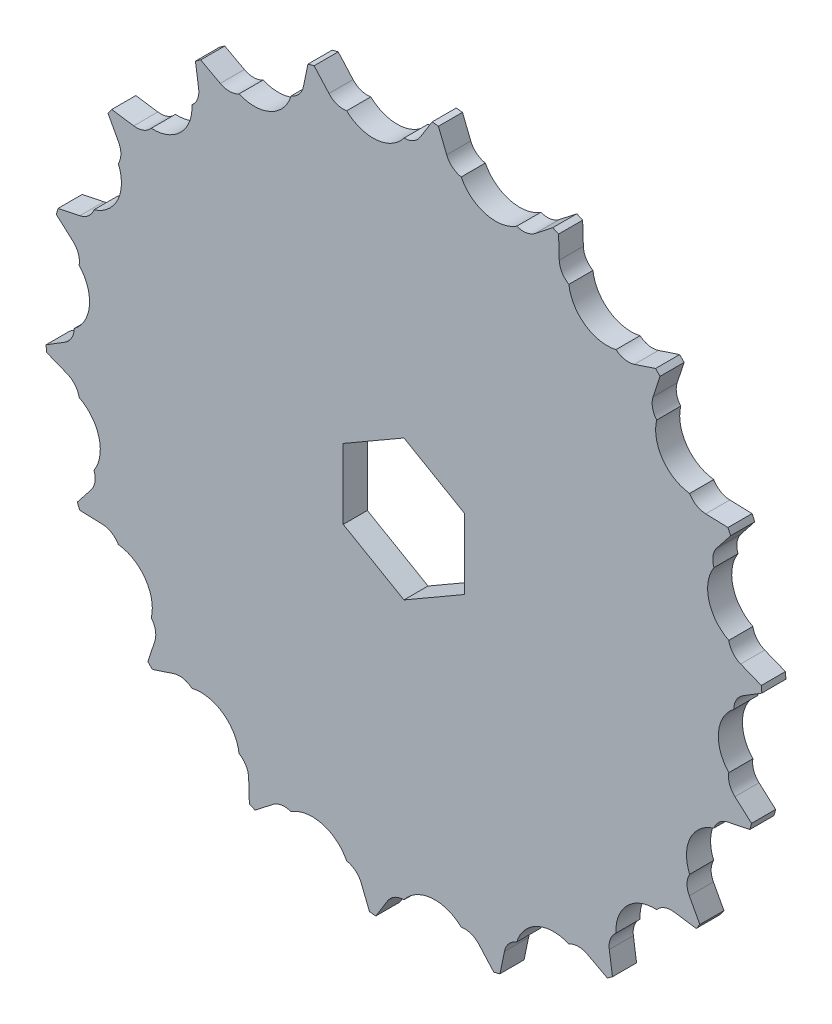
SolidWorks part; units mm, degrees
ref_plane "Front Plane" through (0, 0, 0) normal (0, 0, 1) x (1, 0, 0)
ref_plane "Top Plane" through (0, 0, 0) normal (0, 1, 0) x (1, 0, 0)
ref_plane "Right Plane" through (0, 0, 0) normal (1, 0, 0) x (0, 0, -1)
sketch "Sketch1" plane through (0, 0, 0) normal (0, 0, 1) x (1, 0, 0)
  line L0 (3.4006, 70.3439) -> (6.0855, 74.679)
  line L1 (3.4006, 70.3439) -> (8.8661, 69.8657) construction
  line L2 (6.9749, 74.6012) -> (8.8661, 69.8657)
  line L3 (3.4006, 70.3439) -> (0, 0) construction
  line L4 (0, 0) -> (8.8661, 69.8657) construction
  line L5 (15.5641, 68.6847) -> (18.9609, 72.4877)
  line L6 (19.8233, 72.2567) -> (20.8635, 67.2647)
  line L7 (27.2546, 64.9386) -> (31.2602, 68.094)
  line L8 (32.0693, 67.7166) -> (32.2269, 62.6199)
  line L9 (38.117, 59.2193) -> (42.6097, 61.6312)
  line L10 (43.341, 61.1191) -> (42.6111, 56.0725)
  line L11 (47.8212, 51.7007) -> (52.6645, 53.2958)
  line L12 (53.2958, 52.6645) -> (51.7007, 47.8212)
  line L13 (56.0725, 42.6111) -> (61.1191, 43.341)
  line L14 (61.6312, 42.6097) -> (59.2193, 38.117)
  line L15 (62.6199, 32.2269) -> (67.7166, 32.0693)
  line L16 (68.094, 31.2602) -> (64.9386, 27.2546)
  line L17 (67.2647, 20.8635) -> (72.2567, 19.8233)
  line L18 (72.4877, 18.9609) -> (68.6847, 15.5641)
  line L19 (69.8657, 8.8661) -> (74.6012, 6.9749)
  line L20 (74.679, 6.0855) -> (70.3439, 3.4006)
  line L21 (70.3439, -3.4006) -> (74.679, -6.0855)
  line L22 (74.6012, -6.9749) -> (69.8657, -8.8661)
  line L23 (68.6847, -15.5641) -> (72.4877, -18.9609)
  line L24 (72.2567, -19.8233) -> (67.2647, -20.8635)
  line L25 (64.9386, -27.2546) -> (68.094, -31.2602)
  line L26 (67.7166, -32.0693) -> (62.6199, -32.2269)
  line L27 (59.2193, -38.117) -> (61.6312, -42.6097)
  line L28 (61.1191, -43.341) -> (56.0725, -42.6111)
  line L29 (51.7007, -47.8212) -> (53.2958, -52.6645)
  line L30 (52.6645, -53.2958) -> (47.8212, -51.7007)
  line L31 (42.6111, -56.0725) -> (43.341, -61.1191)
  line L32 (42.6097, -61.6312) -> (38.117, -59.2193)
  line L33 (32.2269, -62.6199) -> (32.0693, -67.7166)
  line L34 (31.2602, -68.094) -> (27.2546, -64.9386)
  line L35 (20.8635, -67.2647) -> (19.8233, -72.2567)
  line L36 (18.9609, -72.4877) -> (15.5641, -68.6847)
  line L37 (8.8661, -69.8657) -> (6.9749, -74.6012)
  line L38 (6.0855, -74.679) -> (3.4006, -70.3439)
  line L39 (-3.4006, -70.3439) -> (-6.0855, -74.679)
  line L40 (-6.9749, -74.6012) -> (-8.8661, -69.8657)
  line L41 (-15.5641, -68.6847) -> (-18.9609, -72.4877)
  line L42 (-19.8233, -72.2567) -> (-20.8635, -67.2647)
  line L43 (-27.2546, -64.9386) -> (-31.2602, -68.094)
  line L44 (-32.0693, -67.7166) -> (-32.2269, -62.6199)
  line L45 (-38.117, -59.2193) -> (-42.6097, -61.6312)
  line L46 (-43.341, -61.1191) -> (-42.6111, -56.0725)
  line L47 (-47.8212, -51.7007) -> (-52.6645, -53.2958)
  line L48 (-53.2958, -52.6645) -> (-51.7007, -47.8212)
  line L49 (-56.0725, -42.6111) -> (-61.1191, -43.341)
  line L50 (-61.6312, -42.6097) -> (-59.2193, -38.117)
  line L51 (-62.6199, -32.2269) -> (-67.7166, -32.0693)
  line L52 (-68.094, -31.2602) -> (-64.9386, -27.2546)
  line L53 (-67.2647, -20.8635) -> (-72.2567, -19.8233)
  line L54 (-72.4877, -18.9609) -> (-68.6847, -15.5641)
  line L55 (-69.8657, -8.8661) -> (-74.6012, -6.9749)
  line L56 (-74.679, -6.0855) -> (-70.3439, -3.4006)
  line L57 (-70.3439, 3.4006) -> (-74.679, 6.0855)
  line L58 (-74.6012, 6.9749) -> (-69.8657, 8.8661)
  line L59 (-68.6847, 15.5641) -> (-72.4877, 18.9609)
  line L60 (-72.2567, 19.8233) -> (-67.2647, 20.8635)
  line L61 (-64.9386, 27.2546) -> (-68.094, 31.2602)
  line L62 (-67.7166, 32.0693) -> (-62.6199, 32.2269)
  line L63 (-59.2193, 38.117) -> (-61.6312, 42.6097)
  line L64 (-61.1191, 43.341) -> (-56.0725, 42.6111)
  line L65 (-51.7007, 47.8212) -> (-53.2958, 52.6645)
  line L66 (-52.6645, 53.2958) -> (-47.8212, 51.7007)
  line L67 (-42.6111, 56.0725) -> (-43.341, 61.1191)
  line L68 (-42.6097, 61.6312) -> (-38.117, 59.2193)
  line L69 (-32.2269, 62.6199) -> (-32.0693, 67.7166)
  line L70 (-31.2602, 68.094) -> (-27.2546, 64.9386)
  line L71 (-20.8635, 67.2647) -> (-19.8233, 72.2567)
  line L72 (-18.9609, 72.4877) -> (-15.5641, 68.6847)
  line L73 (-8.8661, 69.8657) -> (-6.9749, 74.6012)
  line L74 (-6.0855, 74.679) -> (-3.4006, 70.3439)
  line L83 (0, 72.45) -> (0, 0) construction
  line L84 (0, 0) -> (6.5105, 74.4157) construction
  circle A0 centre (0, 0) radius 72.45 construction
  arc A1 (-3.9985, 72.3396) -> (3.4006, 70.3439) centre (0, 72.45) ccw
  arc A2 (4.6139, 72.3029) -> (8.0115, 72.0057) centre (0, 0) cw
  arc A3 (6.0855, 74.679) -> (6.9749, 74.6012) centre (6.5105, 74.4157) cw
  arc A4 (8.6239, 71.9349) -> (15.5641, 68.6847) centre (12.5808, 71.3493) ccw
  arc A5 (18.9609, 72.4877) -> (19.8233, 72.2567) centre (19.3338, 72.1547) cw
  arc A6 (20.9843, 69.3445) -> (27.2546, 64.9386) centre (24.7794, 68.0807) ccw
  arc A7 (31.2602, 68.094) -> (32.0693, 67.7166) centre (31.5696, 67.7012) cw
  arc A8 (32.707, 64.6472) -> (38.117, 59.2193) centre (36.225, 62.7435) ccw
  arc A9 (42.6097, 61.6312) -> (43.341, 61.1191) centre (42.8462, 61.1907) cw
  arc A10 (43.436, 57.9855) -> (47.8212, 51.7007) centre (46.57, 55.4999) ccw
  arc A11 (52.6645, 53.2958) -> (53.2958, 52.6645) centre (52.8209, 52.8209) cw
  arc A12 (52.8452, 49.562) -> (56.0725, 42.6111) centre (55.4999, 46.57) ccw
  arc A13 (61.1191, 43.341) -> (61.6312, 42.6097) centre (61.1907, 42.8462) cw
  arc A14 (60.6487, 39.6326) -> (62.6199, 32.2269) centre (62.7435, 36.225) ccw
  arc A15 (67.7166, 32.0693) -> (68.094, 31.2602) centre (67.7012, 31.5696) cw
  arc A16 (66.6094, 28.4989) -> (67.2647, 20.8635) centre (68.0807, 24.7794) ccw
  arc A17 (72.2567, 19.8233) -> (72.4877, 18.9609) centre (72.1547, 19.3338) cw
  arc A18 (70.5463, 16.4994) -> (69.8657, 8.8661) centre (71.3493, 12.5808) ccw
  arc A19 (74.6012, 6.9749) -> (74.679, 6.0855) centre (74.4157, 6.5105) cw
  arc A20 (72.3396, 3.9985) -> (70.3439, -3.4006) centre (72.45, 0) ccw
  arc A21 (74.679, -6.0855) -> (74.6012, -6.9749) centre (74.4157, -6.5105) cw
  arc A22 (71.9349, -8.6239) -> (68.6847, -15.5641) centre (71.3493, -12.5808) ccw
  arc A23 (72.4877, -18.9609) -> (72.2567, -19.8233) centre (72.1547, -19.3338) cw
  arc A24 (69.3445, -20.9843) -> (64.9386, -27.2546) centre (68.0807, -24.7794) ccw
  arc A25 (68.094, -31.2602) -> (67.7166, -32.0693) centre (67.7012, -31.5696) cw
  arc A26 (64.6472, -32.707) -> (59.2193, -38.117) centre (62.7435, -36.225) ccw
  arc A27 (61.6312, -42.6097) -> (61.1191, -43.341) centre (61.1907, -42.8462) cw
  arc A28 (57.9855, -43.436) -> (51.7007, -47.8212) centre (55.4999, -46.57) ccw
  arc A29 (53.2958, -52.6645) -> (52.6645, -53.2958) centre (52.8209, -52.8209) cw
  arc A30 (49.562, -52.8452) -> (42.6111, -56.0725) centre (46.57, -55.4999) ccw
  arc A31 (43.341, -61.1191) -> (42.6097, -61.6312) centre (42.8462, -61.1907) cw
  arc A32 (39.6326, -60.6487) -> (32.2269, -62.6199) centre (36.225, -62.7435) ccw
  arc A33 (32.0693, -67.7166) -> (31.2602, -68.094) centre (31.5696, -67.7012) cw
  arc A34 (28.4989, -66.6094) -> (20.8635, -67.2647) centre (24.7794, -68.0807) ccw
  arc A35 (19.8233, -72.2567) -> (18.9609, -72.4877) centre (19.3338, -72.1547) cw
  arc A36 (16.4994, -70.5463) -> (8.8661, -69.8657) centre (12.5808, -71.3493) ccw
  arc A37 (6.9749, -74.6012) -> (6.0855, -74.679) centre (6.5105, -74.4157) cw
  arc A38 (3.9985, -72.3396) -> (-3.4006, -70.3439) centre (0, -72.45) ccw
  arc A39 (-6.0855, -74.679) -> (-6.9749, -74.6012) centre (-6.5105, -74.4157) cw
  arc A40 (-8.6239, -71.9349) -> (-15.5641, -68.6847) centre (-12.5808, -71.3493) ccw
  arc A41 (-18.9609, -72.4877) -> (-19.8233, -72.2567) centre (-19.3338, -72.1547) cw
  arc A42 (-20.9843, -69.3445) -> (-27.2546, -64.9386) centre (-24.7794, -68.0807) ccw
  arc A43 (-31.2602, -68.094) -> (-32.0693, -67.7166) centre (-31.5696, -67.7012) cw
  arc A44 (-32.707, -64.6472) -> (-38.117, -59.2193) centre (-36.225, -62.7435) ccw
  arc A45 (-42.6097, -61.6312) -> (-43.341, -61.1191) centre (-42.8462, -61.1907) cw
  arc A46 (-43.436, -57.9855) -> (-47.8212, -51.7007) centre (-46.57, -55.4999) ccw
  arc A47 (-52.6645, -53.2958) -> (-53.2958, -52.6645) centre (-52.8209, -52.8209) cw
  arc A48 (-52.8452, -49.562) -> (-56.0725, -42.6111) centre (-55.4999, -46.57) ccw
  arc A49 (-61.1191, -43.341) -> (-61.6312, -42.6097) centre (-61.1907, -42.8462) cw
  arc A50 (-60.6487, -39.6326) -> (-62.6199, -32.2269) centre (-62.7435, -36.225) ccw
  arc A51 (-67.7166, -32.0693) -> (-68.094, -31.2602) centre (-67.7012, -31.5696) cw
  arc A52 (-66.6094, -28.4989) -> (-67.2647, -20.8635) centre (-68.0807, -24.7794) ccw
  arc A53 (-72.2567, -19.8233) -> (-72.4877, -18.9609) centre (-72.1547, -19.3338) cw
  arc A54 (-70.5463, -16.4994) -> (-69.8657, -8.8661) centre (-71.3493, -12.5808) ccw
  arc A55 (-74.6012, -6.9749) -> (-74.679, -6.0855) centre (-74.4157, -6.5105) cw
  arc A56 (-72.3396, -3.9985) -> (-70.3439, 3.4006) centre (-72.45, 0) ccw
  arc A57 (-74.679, 6.0855) -> (-74.6012, 6.9749) centre (-74.4157, 6.5105) cw
  arc A58 (-71.9349, 8.6239) -> (-68.6847, 15.5641) centre (-71.3493, 12.5808) ccw
  arc A59 (-72.4877, 18.9609) -> (-72.2567, 19.8233) centre (-72.1547, 19.3338) cw
  arc A60 (-69.3445, 20.9843) -> (-64.9386, 27.2546) centre (-68.0807, 24.7794) ccw
  arc A61 (-68.094, 31.2602) -> (-67.7166, 32.0693) centre (-67.7012, 31.5696) cw
  arc A62 (-64.6472, 32.707) -> (-59.2193, 38.117) centre (-62.7435, 36.225) ccw
  arc A63 (-61.6312, 42.6097) -> (-61.1191, 43.341) centre (-61.1907, 42.8462) cw
  arc A64 (-57.9855, 43.436) -> (-51.7007, 47.8212) centre (-55.4999, 46.57) ccw
  arc A65 (-53.2958, 52.6645) -> (-52.6645, 53.2958) centre (-52.8209, 52.8209) cw
  arc A66 (-49.562, 52.8452) -> (-42.6111, 56.0725) centre (-46.57, 55.4999) ccw
  arc A67 (-43.341, 61.1191) -> (-42.6097, 61.6312) centre (-42.8462, 61.1907) cw
  arc A68 (-39.6326, 60.6487) -> (-32.2269, 62.6199) centre (-36.225, 62.7435) ccw
  arc A69 (-32.0693, 67.7166) -> (-31.2602, 68.094) centre (-31.5696, 67.7012) cw
  arc A70 (-28.4989, 66.6094) -> (-20.8635, 67.2647) centre (-24.7794, 68.0807) ccw
  arc A71 (-19.8233, 72.2567) -> (-18.9609, 72.4877) centre (-19.3338, 72.1547) cw
  arc A72 (-16.4994, 70.5463) -> (-8.8661, 69.8657) centre (-12.5808, 71.3493) ccw
  arc A73 (-6.9749, 74.6012) -> (-6.0855, 74.679) centre (-6.5105, 74.4157) cw
  point P289 (0, 0)
  dimension "D1" = 144.9
  dimension "D2" = 4
  dimension "D5" = 0.5
  dimension "D6" = 74.7
  dimension "D3" = 5
  dimension "D4" = 36
extrude "Boss-Extrude1" add sketch "Sketch1" along normal blind 5 contours L74 A73 L73 A72 L72 A71 L71 A70 L70 A69 L69 A68 L68 A67 L67 A66 L66 A65 L65 A64 L64 A63 L63 A62 L62 A61 L61 A60 L60 A59 L59 A58 L58 A57 L57 A56 | A3 L0 A2 L2 region at (-0.0022, -0.0255, 0) region at (6.4054, 73.214, 0)
sketch "Sketch2" plane through (0, 0, 5) normal (0, 0, 1) x (1, 0, 0)
  circle A0 centre (0, 0) radius 12.5
  dimension "D1" = 25
extrude "Boss-Extrude2" add sketch "Sketch2" along normal blind 40
sketch "Sketch5" plane through (0, 0, 0) normal (0, 0, -1) x (-1, 0, 0)
  line L1 (0, 68.45) -> (0.611, 75.4338)
  line L2 (11.8862, 67.4101) -> (12.4972, 74.3939)
  line L3 (0.611, 75.4338) -> (12.4972, 74.3939)
  arc A0 (0, 68.45) -> (11.8862, 67.4101) centre (6.4077, 73.2398) ccw
  arc A3 (-3.4006, 70.3439) -> (3.4006, 70.3439) centre (0, 72.45) ccw construction
  arc A5 (-3.4006, 70.3439) -> (3.4006, 70.3439) centre (0, 72.45) ccw construction
  arc A7 (8.8661, 69.8657) -> (15.5641, 68.6847) centre (12.5808, 71.3493) ccw construction
  arc A8 (6.9749, 74.6012) -> (6.0855, 74.679) centre (6.5105, 74.4157) ccw construction
  point P0 (0.4708, 75.3302)
  point P8 (3, 68.45)
  point P9 (0, 0)
  point P12 (12.4972, 67.0634)
  point P15 (0.611, 68.4969)
  point P19 (0, 68.45)
  point P22 (11.8862, 67.4101)
  dimension "D4" = 8
extrude "Cut-Extrude2" cut sketch "Sketch5" against normal blind 10
sketch "Sketch9" plane through (0, 0, 0) normal (0, 0, -1) x (-1, 0, 0)
  circle A0 centre (0, 0) radius 74.5
  circle A1 centre (0, 0) radius 100
  dimension "D1" = 149
  dimension "D2" = 200
extrude "Cut-Extrude5" cut sketch "Sketch9" against normal blind 10
fillet "Fillet1" radius 30 1 edges at (12.5, 0, 5)
sketch "Sketch3" plane through (0, 0, 45) normal (0, 0, 1) x (1, 0, 0)
  circle A0 centre (0, 0) radius 5
  dimension "D1" = 10
extrude "Cut-Extrude1" cut sketch "Sketch3" against normal through all
hole_wizard "Ø1.0mm Dowel Hole1" positions "3DSketch1" profile "Sketch4" hole size "Ø1.0" standard "ANSI Metric"
sketch3d "3DSketch1"
  point P0 (-6.8176, -10.4771, 42.0201)
  point P2 (-11.0684, 5.8086, 41.6583)
sketch "Sketch4" plane through (-6.8176, -10.4771, 42.0201) normal (0, 0, 1) x (0.8382, -0.5454, 0)
  line L0 (0, 0) -> (0, 34)
  line L1 (0, 34) -> (1.4, 33.1588)
  line L2 (1.4, 33.1588) -> (1.4, 0)
  line L5 (1.4, 0) -> (0, 0)
  line L10 (0, 34) -> (-1.4, 33.1588) construction
  line L11 (0, -6.35) -> (0, 107.95) construction
  dimension "Hole Dia." = 2.8
  dimension "Hole Depth" = 34
  dimension "Drill Angle" = 118
pattern_circular "CirPattern1" count 18 over 360 about axis through (0, 0, 0) along (0, 0, 1) of "Cut-Extrude2"
sketch "Sketch6" plane through (0, 0, 0) normal (0, 1, 0) x (1, 0, 0)
  line L0 (-71.7872, -5) -> (-67.2647, -5) construction
  line L1 (-74.2713, -5) -> (79.9055, -5)
  line L2 (-74.2713, -5) -> (-74.2713, -50.9165)
  line L3 (-74.2713, -50.9165) -> (79.9055, -50.9165)
  line L4 (79.9055, -5) -> (79.9055, -50.9165)
  point P4 (-74.2713, -6.1408)
extrude "Cut-Extrude3" cut sketch "Sketch6" against normal through all both and the other way through all
sketch "Sketch7" plane through (0, 0, 0) normal (0, 0, -1) x (-1, 0, 0)
  line L1 (12.6, -7.2746) -> (12.6, 7.2746)
  line L2 (12.6, 7.2746) -> (0, 14.5492)
  line L3 (0, 14.5492) -> (-12.6, 7.2746)
  line L4 (-12.6, 7.2746) -> (-12.6, -7.2746)
  line L5 (-12.6, -7.2746) -> (0, -14.5492)
  line L6 (0, -14.5492) -> (12.6, -7.2746)
  circle A0 centre (0, 0) radius 12.6 construction
  dimension "D1" = 25.2
extrude "Cut-Extrude4" cut sketch "Sketch7" against normal through all both
sketch "Sketch10" plane through (0, 0, 0) normal (0, 0, -1) x (-1, 0, 0)
  circle A0 centre (0, 0) radius 55
  dimension "D1" = 110
extrude "Cut-Extrude6" [suppressed] cut sketch "Sketch10" against normal blind 10
equation "\"Teeth\"= 36"
equation "\"D4@Sketch1\"=\"Teeth\""
equation "\"D6@Sketch1\"=83/40*\"Teeth\""
equation "\"D1@Sketch1\"=161/40*\"Teeth\""
equation "\"D3@Sketch1\"=4.5/\"Teeth\"*40"
equation "\"D1@CirPattern1\"=\"Teeth\"/2"
